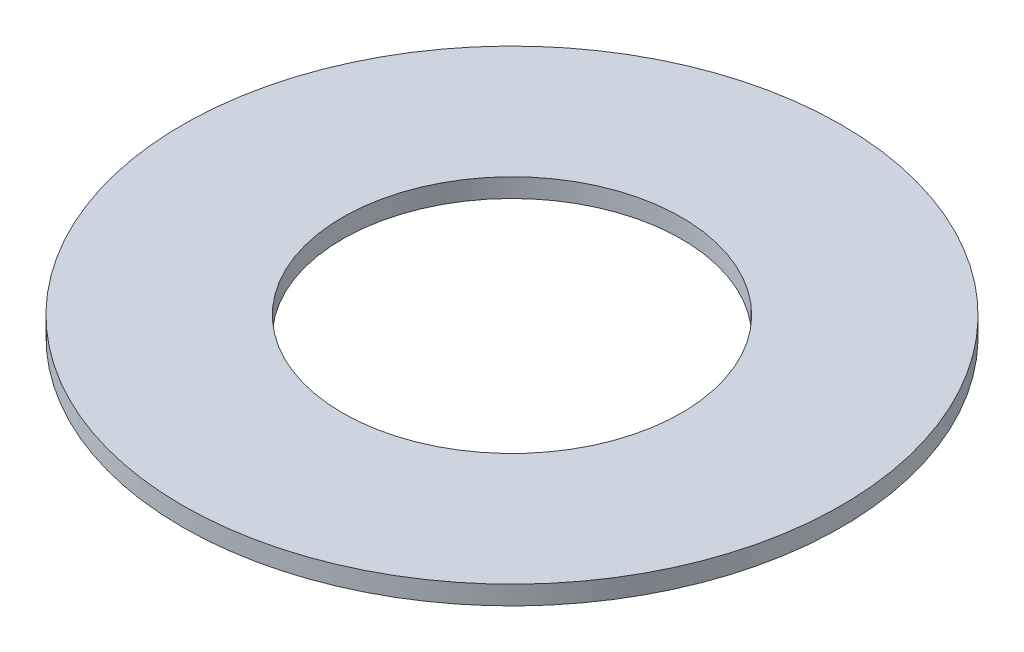
SolidWorks part; units mm, degrees
ref_plane "Front Plane" through (0, 0, 0) normal (0, 0, 1) x (1, 0, 0)
ref_plane "Top Plane" through (0, 0, 0) normal (0, 1, 0) x (1, 0, 0)
ref_plane "Right Plane" through (0, 0, 0) normal (1, 0, 0) x (0, 0, -1)
sketch "Sketch1" plane through (0, 0, 0) normal (0, 1, 0) x (1, 0, 0)
  circle A0 centre (0, 0) radius 87.5
  dimension "FLANGE_OD" = 175
extrude "Boss-Extrude1" add sketch "Sketch1" along normal blind 5
sketch "Sketch2" plane through (0, 0, 0) normal (0, 1, 0) x (1, 0, 0)
  circle A0 centre (0, 0) radius 45
  dimension "BORE_D" = 90
extrude "Cut-Extrude1" cut sketch "Sketch2" along normal through all
sketch "Sketch3" plane through (0, 5, 0) normal (0, 1, 0) x (1, 0, 0)
  circle A0 centre (0, 0) radius 37.2604 construction
  circle A1 centre (-37.2604, 0) radius 6.9336
  dimension "BOLT_D" = 13.8673
  dimension "BOLT_PCD" = 74.5208
extrude "Cut-Extrude2" cut sketch "Sketch3" against normal blind 3.345 rebuild error yes
pattern_circular "CirPattern1" count 4 over 360 rebuild error yes
